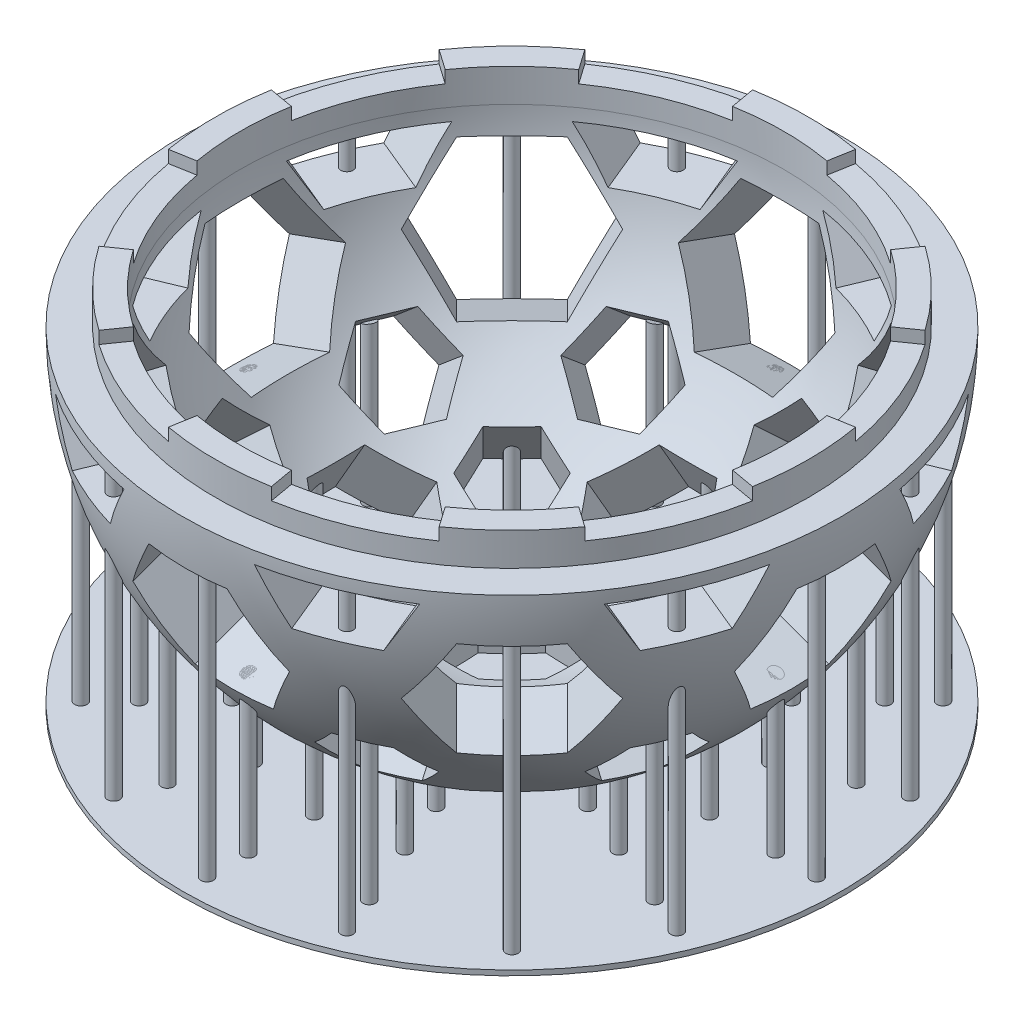
SolidWorks part; units mm, degrees
ref_plane "Front Plane" through (0, 0, 0) normal (0, 0, 1) x (1, 0, 0)
ref_plane "Top Plane" through (0, 0, 0) normal (0, 1, 0) x (1, 0, 0)
ref_plane "Right Plane" through (0, 0, 0) normal (1, 0, 0) x (0, 0, -1)
sketch "Sketch1" plane through (0, 0, 0) normal (0, 0, 1) x (1, 0, 0)
  line L0 (0, -40) -> (0, -33)
  line L2 (-40, 0) -> (-33, 0)
  arc A0 (-40, 0) -> (0, -40) centre (0, 0) ccw
  arc A1 (-33, 0) -> (0, -33) centre (0, 0) ccw
  dimension "D1" = 80
  dimension "D2" = 66
revolve "Revolve1" add sketch "Sketch1" angle 360 about L0
sketch "Sketch2" plane through (0, 0, 0) normal (0, 1, 0) x (1, 0, 0)
  line L0 (-40, 0) -> (40, 0) construction
sketch "Sketch3" plane through (0, 0, 0) normal (0, 1, 0) x (1, 0, 0)
  line L0 (0, -40) -> (0, 40) construction
sketch "Sketch4" plane through (0, 0, 0) normal (0, 0, 1) x (1, 0, 0)
  line L0 (0, -40) -> (0, 40) construction
sketch "Sketch5" plane through (0, 0, 0) normal (0, 1, 0) x (1, 0, 0)
  point P0 (0, 0)
ref_plane "Plane CUT 1" through (0, 0, 0) normal (0, -0.342, 0.9397) x (1, 0, 0)
sketch "Sketch6" plane through (0, 0, 0) normal (0, -0.342, 0.9397) x (1, 0, 0)
  line L7 (4.75, -8.2272) -> (9.5, 0)
  line L8 (9.5, 0) -> (4.75, 8.2272)
  line L9 (4.75, 8.2272) -> (-4.75, 8.2272)
  line L10 (-4.75, 8.2272) -> (-9.5, 0)
  line L11 (-9.5, 0) -> (-4.75, -8.2272)
  line L12 (-4.75, -8.2272) -> (4.75, -8.2272)
  circle A0 centre (0, 0) radius 8.2272 construction
extrude "Cut-Extrude1" cut sketch "Sketch6" along normal blind 60
pattern_circular "CirPattern1" count 8 over 360 about axis through (0, -40, 0) along (0, 1, 0) of "Cut-Extrude1" reverse direction yes
ref_plane "Plane2" through (0, 0, 0) normal (0.9239, 0, -0.3827) x (0, 1, 0)
sketch "Sketch7" plane through (0, 0, 0) normal (0.9239, 0, -0.3827) x (0, 1, 0)
  line L0 (0, -51.8688) -> (0, 51.8688) construction
ref_plane "Plane CUT 2" through (0, 0, 0) normal (0.7077, 0.6428, -0.2932) x (0.3827, 0, 0.9239)
sketch "Sketch8" plane through (0, 0, 0) normal (0.7077, 0.6428, -0.2932) x (0.3827, 0, 0.9239)
  line L1 (-2.8868, -5) -> (2.8868, -5)
  line L2 (2.8868, -5) -> (5.7735, 0)
  line L3 (5.7735, 0) -> (2.8868, 5)
  line L4 (2.8868, 5) -> (-2.8868, 5)
  line L5 (-2.8868, 5) -> (-5.7735, 0)
  line L6 (-5.7735, 0) -> (-2.8868, -5)
  circle A0 centre (0, 0) radius 5 construction
extrude "Cut-Extrude2" cut sketch "Sketch8" against normal blind 60
pattern_circular "CirPattern2" count 8 over 360 about axis through (0, -40, 0) along (0, 1, 0) of "Cut-Extrude2" reverse direction yes
ref_plane "PLANE CUT 4" through (0, 0, 0) normal (0, -0.866, 0.5) x (1, 0, 0)
sketch "Sketch9" plane through (0, 0, 0) normal (0, -0.866, 0.5) x (1, 0, 0)
  line L1 (3.5, -6.0622) -> (7, 0)
  line L2 (7, 0) -> (3.5, 6.0622)
  line L3 (3.5, 6.0622) -> (-3.5, 6.0622)
  line L4 (-3.5, 6.0622) -> (-7, 0)
  line L5 (-7, 0) -> (-3.5, -6.0622)
  line L6 (-3.5, -6.0622) -> (3.5, -6.0622)
  circle A0 centre (0, 0) radius 6.0622 construction
extrude "Cut-Extrude3" cut sketch "Sketch9" along normal blind 72
pattern_circular "CirPattern3" count 8 over 360 about axis through (0, -40, 0) along (0, 1, 0) skipping 1, 3, 5, 7 of "Cut-Extrude3" reverse direction yes
sketch "Sketch10" plane through (0, 0, 0) normal (0, 1, 0) x (1, 0, 0)
  line L0 (2.8995, -7) -> (7, -2.8995)
  line L1 (7, 2.8995) -> (2.8995, 7)
  line L2 (2.8995, 7) -> (-2.8995, 7)
  line L3 (-2.8995, 7) -> (-7, 2.8995)
  line L4 (-7, 2.8995) -> (-7, -2.8995)
  line L5 (-7, -2.8995) -> (-2.8995, -7)
  line L6 (-2.8995, -7) -> (2.8995, -7)
  line L7 (7, -2.8995) -> (7, 2.8995)
  circle A0 centre (0, 0) radius 7 construction
extrude "Cut-Extrude4" cut sketch "Sketch10" against normal blind 72
ref_plane "Plane5" through (0, 0, 0) normal (0.7071, 0, 0.7071) x (0, 1, 0)
sketch "Sketch11" plane through (0, 0, 0) normal (0.7071, 0, 0.7071) x (0, 1, 0)
  line L0 (0, -40) -> (0, 40) construction
ref_plane "PLANE CUT 3" through (0, 0, 0) normal (0.3747, 0.848, 0.3747) x (-0.7071, 0, 0.7071)
sketch "Sketch12" plane through (0, 0, 0) normal (0.3747, 0.848, 0.3747) x (-0.7071, 0, 0.7071)
  line L1 (-5, 0) -> (-2.5, -4.3301)
  line L2 (-2.5, -4.3301) -> (2.5, -4.3301)
  line L3 (2.5, -4.3301) -> (5, 0)
  line L4 (5, 0) -> (2.5, 4.3301)
  line L5 (2.5, 4.3301) -> (-2.5, 4.3301)
  line L6 (-2.5, 4.3301) -> (-5, 0)
  circle A0 centre (0, 0) radius 4.3301 construction
extrude "Cut-Extrude5" cut sketch "Sketch12" against normal blind 72
pattern_circular "CirPattern4" count 4 over 360 about axis through (0, -40, 0) along (0, 1, 0) of "Cut-Extrude5" reverse direction yes
ref_plane "Plane6" through (0, 0, 0) normal (0.3827, 0, 0.9239) x (0, 1, 0)
sketch "Sketch13" plane through (0, 0, 0) normal (0.3827, 0, 0.9239) x (0, 1, 0)
  line L0 (-1.5, 7.6797) -> (-1.5, -7.6797)
  line L2 (-1.5, 7.6797) -> (-7.4008, 4.2729)
  line L3 (-7.4008, 4.2729) -> (-7.4008, -4.2729)
  line L4 (-7.4008, -4.2729) -> (-1.5, -7.6797)
  line L7 (0, 36.9552) -> (0, -36.9552) construction
  line L8 (7.4008, 4.2729) -> (3.7004, 6.4093) [skipped]
  line L9 (7.4008, -4.2729) -> (7.4008, 0) [skipped]
  line L10 (0, -8.5457) -> (3.7004, -6.4093) [skipped]
  arc A0 (-1.5, 7.2472) -> (-1.5, -7.2472) centre (0, 0) ccw construction
  dimension "D1" = 1.5
extrude "Cut-Extrude6" cut sketch "Sketch13" against normal up to vertex (51.8688 mm away) up to point (-19.8493, 0, -47.9205)
pattern_circular "CirPattern5" count 8 over 360 about axis through (0, -40, 0) along (0, 1, 0) of "Cut-Extrude6" reverse direction yes
ref_plane "Plane7" through (0, -40, 0) normal (0, 1, 0) x (1, 0, 0)
sketch "Sketch14" plane through (0, -40, 0) normal (0, 1, 0) x (1, 0, 0)
  circle A0 centre (0, 0) radius 40
extrude "Boss-Extrude1" add sketch "Sketch14" along normal blind 0.6173 separate body
sketch "Sketch15" plane through (0, -39.3827, 0) normal (0, 1, 0) x (1, 0, 0)
  circle A0 centre (37, 0) radius 0.75
  circle A1 centre (0, 0) radius 40 construction
  dimension "D1" = 0
  dimension "D3" = 1.5
  dimension "D2" = 37
extrude "Boss-Extrude8" add sketch "Sketch15" along normal blind 38.8
pattern_circular "CirPattern6" count 16 over 360 about axis through (0, -40, 0) along (0, 1, 0) of "Boss-Extrude8" reverse direction yes
sketch "Sketch16" plane through (0, -39.3827, 0) normal (0, 1, 0) x (1, 0, 0)
  circle A0 centre (-32, 0) radius 0.75
  dimension "D1" = 1.5
  dimension "D2" = 0
  dimension "D3" = 32
extrude "Boss-Extrude13" add sketch "Sketch16" along normal blind 23
pattern_circular "CirPattern10" count 16 over 360 about axis through (0, -40, 0) along (0, 1, 0) of "Boss-Extrude13" reverse direction yes
sketch "Sketch17" plane through (0, -39.3827, 0) normal (0, 1, 0) x (1, 0, 0)
  circle A0 centre (0, 24) radius 0.75
  dimension "D1" = 1.5
  dimension "D2" = 0
  dimension "D3" = 24
extrude "Boss-Extrude16" add sketch "Sketch17" along normal blind 12
pattern_circular "CirPattern11" count 16 over 360 about axis through (0, -40, 0) along (0, 1, 0) of "Boss-Extrude16" reverse direction yes
sketch "Sketch18" plane through (0, -39.3827, 0) normal (0, 1, 0) x (1, 0, 0)
  circle A0 centre (13, 0) radius 0.75
  dimension "D1" = 1.5
  dimension "D2" = 0
  dimension "D3" = 13
extrude "Boss-Extrude17" add sketch "Sketch18" along normal blind 2.5
pattern_circular "CirPattern12" count 16 over 360 about axis through (0, -40, 0) along (0, 1, 0) of "Boss-Extrude17" reverse direction yes
sketch "Sketch19" plane through (0, -39.3827, 0) normal (0, 1, 0) x (1, 0, 0)
  line L1 (0, 0) -> (15.706, -6.5056) construction
  line L2 (-40, 0) -> (40, 0) construction
  circle A1 centre (0, 0) radius 17 construction
  circle A2 centre (15.706, -6.5056) radius 0.75
  dimension "D1" = 34
  dimension "D2" = 22.5
  dimension "D3" = 1.5
extrude "Boss-Extrude19" add sketch "Sketch19" along normal blind 5
pattern_circular "CirPattern13" count 8 over 360 about axis through (0, -40, 0) along (0, 1, 0) of "Boss-Extrude19" reverse direction yes
sketch "Sketch20" plane through (-1.9897, -7.7311, -1.9897) normal (0.2418, 0.9397, 0.2418) x (0.9703, -0.2342, -0.0603)
  circle A0 centre (24.9892, -27.1181) radius 2
  dimension "D1" = 4
extrude "Cut-Extrude7" cut sketch "Sketch20" along normal blind 5
pattern_circular "CirPattern14" count 16 over 360 about axis through (0, -40, 0) along (0, 1, 0) of "Cut-Extrude7" reverse direction yes
sketch "Sketch22" plane through (0, -1.5, 0) normal (0, -1, 0) x (1, 0, 0)
  line L0 (0, 0) -> (-9.5763, 35.7393) construction
  line L1 (0, 40) -> (0, -40) construction
  circle A0 centre (0, 0) radius 37 construction
  circle A1 centre (-9.5763, 35.7393) radius 0.75
  dimension "D1" = 74
  dimension "D3" = 1.5
  dimension "D2" = 15
ref_plane "Plane9" through (0, -7.4008, 0) normal (0, 1, 0) x (1, 0, 0)
sketch "Sketch24" plane through (0, -7.4008, 0) normal (0, 1, 0) x (1, 0, 0)
  line L0 (-11.3564, -34.9513) -> (-11.5881, -35.6646) construction
  line L1 (0, -40) -> (0, 40) construction
  arc A0 (-12.2991, -35.4257) -> (-10.8726, -35.8892) centre (0, 0) ccw construction
  circle A1 centre (-11.5881, -35.6646) radius 0.75
  dimension "D2" = 1.5
  dimension "D3" = 75
  dimension "D1" = 18
extrude "Boss-Extrude39" [suppressed] add sketch "Sketch24" along normal up to next and the other way blind 0.5
pattern_circular "CirPattern15" [suppressed] count 40 over 360 about axis through (0, -40, 0) along (0, 1, 0) reverse direction yes of bodies 127
sketch "Sketch30" plane through (-2.8139, -7.7311, 0) normal (0.342, 0.9397, 0) x (0.9397, -0.342, 0)
  circle A0 centre (35.6558, -2.7696) radius 0.9041
extrude "Boss-Extrude40" [suppressed] add sketch "Sketch30" along normal up to next
pattern_circular "CirPattern16" [suppressed] count 40 over 360 about axis through (0, -40, 0) along (0, 1, 0) reverse direction yes of bodies 129
sketch "Sketch31" plane through (0, 0, 0) normal (0, 1, 0) x (1, 0, 0)
  line L0 (-40, 0) -> (40, 0) construction
  circle A0 centre (0, 0) radius 36
  circle A1 centre (0, 0) radius 33
  dimension "D1" = 72
  dimension "D2" = 66
extrude "Boss-Extrude41" add sketch "Sketch31" along normal blind 2.5
sketch "Sketch32" plane through (0, 2.5, 0) normal (0, 1, 0) x (1, 0, 0)
  line L2 (-40, 0) -> (40, 0) construction
  line L3 (-32.4987, 5.7304) -> (-35.4531, 6.2513)
  line L4 (-32.4987, -5.7304) -> (-35.4531, -6.2513)
  arc A0 (-35.4531, 6.2513) -> (-35.4531, -6.2513) centre (0, 0) ccw
  arc A1 (-32.4987, 5.7304) -> (-32.4987, -5.7304) centre (0, 0) ccw
  dimension "D1" = 33
  dimension "D2" = 36
  dimension "D3" = 10
  dimension "D4" = 10
extrude "Boss-Extrude42" add sketch "Sketch32" along normal blind 1.5
pattern_circular "CirPattern17" count 8 over 360 about axis through (0, -40, 0) along (0, 1, 0) of "Boss-Extrude42" reverse direction yes
